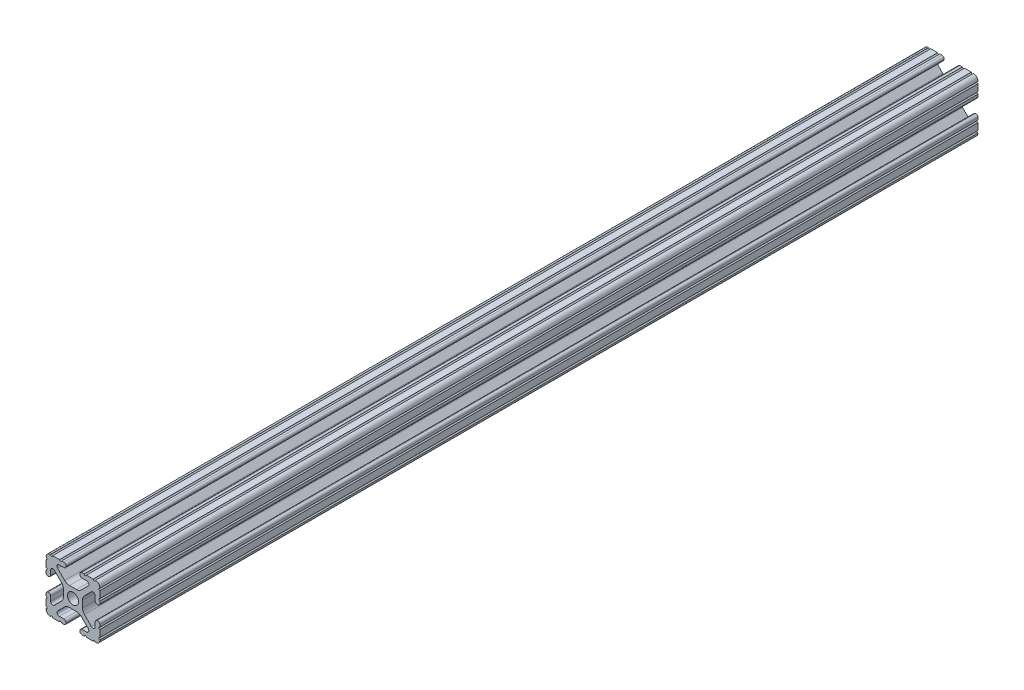
SolidWorks part; units mm, degrees
ref_plane "Front Plane" through (0, 0, 0) normal (0, 0, 1) x (1, 0, 0)
ref_plane "Top Plane" through (0, 0, 0) normal (0, 1, 0) x (1, 0, 0)
ref_plane "Right Plane" through (0, 0, 0) normal (1, 0, 0) x (0, 0, -1)
sketch "Sketch1" plane through (0, 0, 0) normal (0, 0, 1) x (1, 0, 0)
  line L88 (-7.1797, -8.6452) -> (-3.9523, -5.4237)
  line L89 (-1.7093, -4.4958) -> (1.7093, -4.4958)
  line L90 (3.9523, -5.4237) -> (7.1797, -8.6452)
  line L91 (6.4164, -10.4902) -> (4.2875, -10.4902)
  line L92 (3.2385, -11.5392) -> (3.2385, -11.651)
  line L93 (4.2875, -12.7) -> (5.3171, -12.7)
  line L94 (6.3331, -12.7) -> (9.5504, -12.7)
  line L95 (12.7, -9.5504) -> (12.7, -6.3331)
  line L96 (12.7, -5.3171) -> (12.7, -4.2875)
  line L97 (11.651, -3.2385) -> (11.5392, -3.2385)
  line L98 (10.4902, -4.2875) -> (10.4902, -6.4021)
  line L99 (8.7371, -7.1294) -> (5.441, -3.8408)
  line L100 (4.5085, -1.5932) -> (4.5085, 1.5932)
  line L101 (5.441, 3.8408) -> (8.7371, 7.1294)
  line L102 (10.4902, 6.4021) -> (10.4902, 4.2875)
  line L103 (11.5392, 3.2385) -> (11.651, 3.2385)
  line L104 (12.7, 4.2875) -> (12.7, 5.3171)
  line L105 (12.7, 6.3331) -> (12.7, 9.5504)
  line L106 (9.5504, 12.7) -> (6.3331, 12.7)
  line L107 (5.3171, 12.7) -> (4.2875, 12.7)
  line L108 (3.2385, 11.651) -> (3.2385, 11.5392)
  line L109 (4.2875, 10.4902) -> (6.4768, 10.4902)
  line L110 (7.207, 8.7244) -> (3.8983, 5.4232)
  line L111 (1.6558, 4.4958) -> (-1.6558, 4.4958)
  line L112 (-3.8983, 5.4232) -> (-7.207, 8.7244)
  line L113 (-6.4768, 10.4902) -> (-4.2875, 10.4902)
  line L114 (-3.2385, 11.5392) -> (-3.2385, 11.651)
  line L115 (-4.2875, 12.7) -> (-5.3171, 12.7)
  line L116 (-6.3331, 12.7) -> (-9.5504, 12.7)
  line L117 (-12.7, 9.5504) -> (-12.7, 6.3331)
  line L118 (-12.7, 5.3171) -> (-12.7, 4.2875)
  line L119 (-11.651, 3.2385) -> (-11.5392, 3.2385)
  line L120 (-10.4902, 4.2875) -> (-10.4902, 6.4021)
  line L121 (-8.7371, 7.1294) -> (-5.441, 3.8408)
  line L122 (-4.5085, 1.5932) -> (-4.5085, -1.5932)
  line L123 (-5.441, -3.8408) -> (-8.7371, -7.1294)
  line L124 (-10.4902, -6.4021) -> (-10.4902, -4.2875)
  line L125 (-11.5392, -3.2385) -> (-11.651, -3.2385)
  line L126 (-12.7, -4.2875) -> (-12.7, -5.3171)
  line L127 (-12.7, -6.3331) -> (-12.7, -9.5504)
  line L128 (-9.5504, -12.7) -> (-6.3331, -12.7)
  line L129 (-5.3171, -12.7) -> (-4.2875, -12.7)
  line L130 (-3.2385, -11.651) -> (-3.2385, -11.5392)
  line L131 (-4.2875, -10.4902) -> (-6.4164, -10.4902)
  circle A1 centre (0, 0) radius 2.6035
  arc A104 (-7.1797, -8.6452) -> (-6.4164, -10.4902) centre (-6.4164, -9.4098) ccw
  arc A105 (-1.7093, -4.4958) -> (-3.9523, -5.4237) centre (-1.7093, -7.6708) ccw
  arc A106 (3.9523, -5.4237) -> (1.7093, -4.4958) centre (1.7093, -7.6708) ccw
  arc A107 (6.4164, -10.4902) -> (7.1797, -8.6452) centre (6.4164, -9.4098) ccw
  arc A108 (4.2875, -10.4902) -> (3.2385, -11.5392) centre (4.2875, -11.5392) ccw
  arc A109 (3.2385, -11.651) -> (4.2875, -12.7) centre (4.2875, -11.651) ccw
  arc A110 (6.3331, -12.7) -> (5.3171, -12.7) centre (5.8251, -12.7) ccw
  arc A111 (10.5664, -12.6998) -> (9.5504, -12.7) centre (10.0584, -12.7) ccw
  arc A112 (10.5664, -12.6998) -> (12.6998, -10.5664) centre (10.5918, -10.5918) ccw
  arc A113 (12.7, -9.5504) -> (12.6998, -10.5664) centre (12.7, -10.0584) ccw
  arc A114 (12.7, -5.3171) -> (12.7, -6.3331) centre (12.7, -5.8251) ccw
  arc A115 (12.7, -4.2875) -> (11.651, -3.2385) centre (11.651, -4.2875) ccw
  arc A116 (11.5392, -3.2385) -> (10.4902, -4.2875) centre (11.5392, -4.2875) ccw
  arc A117 (8.7371, -7.1294) -> (10.4902, -6.4021) centre (9.4628, -6.4021) ccw
  arc A118 (4.5085, -1.5932) -> (5.441, -3.8408) centre (7.6835, -1.5932) ccw
  arc A119 (5.441, 3.8408) -> (4.5085, 1.5932) centre (7.6835, 1.5932) ccw
  arc A120 (10.4902, 6.4021) -> (8.7371, 7.1294) centre (9.4628, 6.4021) ccw
  arc A121 (10.4902, 4.2875) -> (11.5392, 3.2385) centre (11.5392, 4.2875) ccw
  arc A122 (11.651, 3.2385) -> (12.7, 4.2875) centre (11.651, 4.2875) ccw
  arc A123 (12.7, 6.3331) -> (12.7, 5.3171) centre (12.7, 5.8251) ccw
  arc A124 (12.6998, 10.5664) -> (12.7, 9.5504) centre (12.7, 10.0584) ccw
  arc A125 (12.6998, 10.5664) -> (10.5664, 12.6998) centre (10.5918, 10.5918) ccw
  arc A126 (9.5504, 12.7) -> (10.5664, 12.6998) centre (10.0584, 12.7) ccw
  arc A127 (5.3171, 12.7) -> (6.3331, 12.7) centre (5.8251, 12.7) ccw
  arc A128 (4.2875, 12.7) -> (3.2385, 11.651) centre (4.2875, 11.651) ccw
  arc A129 (3.2385, 11.5392) -> (4.2875, 10.4902) centre (4.2875, 11.5392) ccw
  arc A130 (7.207, 8.7244) -> (6.4768, 10.4902) centre (6.4768, 9.4563) ccw
  arc A131 (1.6558, 4.4958) -> (3.8983, 5.4232) centre (1.6558, 7.6708) ccw
  arc A132 (-3.8983, 5.4232) -> (-1.6558, 4.4958) centre (-1.6558, 7.6708) ccw
  arc A133 (-6.4768, 10.4902) -> (-7.207, 8.7244) centre (-6.4768, 9.4563) ccw
  arc A134 (-4.2875, 10.4902) -> (-3.2385, 11.5392) centre (-4.2875, 11.5392) ccw
  arc A135 (-3.2385, 11.651) -> (-4.2875, 12.7) centre (-4.2875, 11.651) ccw
  arc A136 (-6.3331, 12.7) -> (-5.3171, 12.7) centre (-5.8251, 12.7) ccw
  arc A137 (-10.5664, 12.6998) -> (-9.5504, 12.7) centre (-10.0584, 12.7) ccw
  arc A138 (-10.5664, 12.6998) -> (-12.6998, 10.5664) centre (-10.5918, 10.5918) ccw
  arc A139 (-12.7, 9.5504) -> (-12.6998, 10.5664) centre (-12.7, 10.0584) ccw
  arc A140 (-12.7, 5.3171) -> (-12.7, 6.3331) centre (-12.7, 5.8251) ccw
  arc A141 (-12.7, 4.2875) -> (-11.651, 3.2385) centre (-11.651, 4.2875) ccw
  arc A142 (-11.5392, 3.2385) -> (-10.4902, 4.2875) centre (-11.5392, 4.2875) ccw
  arc A143 (-8.7371, 7.1294) -> (-10.4902, 6.4021) centre (-9.4628, 6.4021) ccw
  arc A144 (-4.5085, 1.5932) -> (-5.441, 3.8408) centre (-7.6835, 1.5932) ccw
  arc A145 (-5.441, -3.8408) -> (-4.5085, -1.5932) centre (-7.6835, -1.5932) ccw
  arc A146 (-10.4902, -6.4021) -> (-8.7371, -7.1294) centre (-9.4628, -6.4021) ccw
  arc A147 (-10.4902, -4.2875) -> (-11.5392, -3.2385) centre (-11.5392, -4.2875) ccw
  arc A148 (-11.651, -3.2385) -> (-12.7, -4.2875) centre (-11.651, -4.2875) ccw
  arc A149 (-12.7, -6.3331) -> (-12.7, -5.3171) centre (-12.7, -5.8251) ccw
  arc A150 (-12.6998, -10.5664) -> (-12.7, -9.5504) centre (-12.7, -10.0584) ccw
  arc A151 (-12.6998, -10.5664) -> (-10.5664, -12.6998) centre (-10.5918, -10.5918) ccw
  arc A152 (-9.5504, -12.7) -> (-10.5664, -12.6998) centre (-10.0584, -12.7) ccw
  arc A153 (-5.3171, -12.7) -> (-6.3331, -12.7) centre (-5.8251, -12.7) ccw
  arc A154 (-4.2875, -12.7) -> (-3.2385, -11.651) centre (-4.2875, -11.651) ccw
  arc A155 (-3.2385, -11.5392) -> (-4.2875, -10.4902) centre (-4.2875, -11.5392) ccw
extrude "Boss-Extrude1" add sketch "Sketch1" along normal mid plane 414.02
